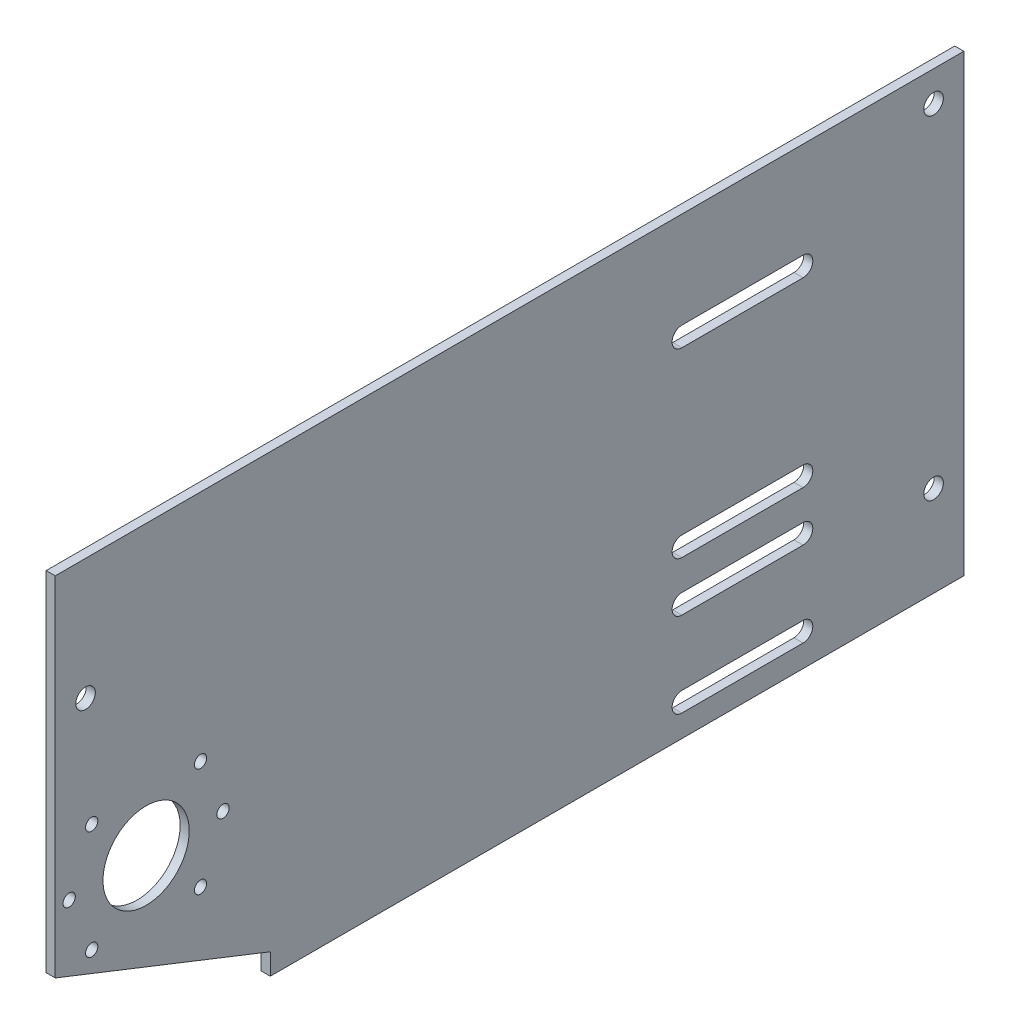
SolidWorks part; units mm, degrees
ref_plane "Front Plane" through (0, 0, 0) normal (0, 0, 1) x (1, 0, 0)
ref_plane "Top Plane" through (0, 0, 0) normal (0, 1, 0) x (1, 0, 0)
ref_plane "Right Plane" through (0, 0, 0) normal (1, 0, 0) x (0, 0, -1)
sketch "Sketch1" plane through (0, 0, 0) normal (1, 0, 0) x (0, 0, -1)
  line L1 (0, 0) -> (300, 0)
  line L2 (0, 0) -> (0, 150)
  line L3 (0, 150) -> (300, 150)
  line L4 (300, 0) -> (300, 150)
  circle A0 centre (30, 55) radius 14.235
  dimension "D1" = 300
  dimension "D5" = 28.47
  dimension "D4" = 55
  dimension "D2" = 150
  dimension "D3" = 30
extrude "Boss-Extrude1" add sketch "Sketch1" along normal blind 3
sketch "Sketch2" plane through (0, 0, 0) normal (-1, 0, 0) x (0, 0, 1)
  line L0 (-246.901, 55) -> (-206.901, 55) construction
  line L1 (-246.901, 58.225) -> (-206.901, 58.225)
  line L2 (-246.901, 51.775) -> (-206.901, 51.775)
  line L3 (-206.901, 115) -> (-246.901, 115) construction
  line L4 (-206.901, 111.77) -> (-246.901, 111.77)
  line L5 (-206.901, 118.23) -> (-246.901, 118.23)
  line L6 (-246.901, 38.55) -> (-206.901, 38.55) construction
  line L9 (-246.901, 41.775) -> (-206.901, 41.775)
  line L10 (-246.901, 35.325) -> (-206.901, 35.325)
  line L11 (-246.901, 10.55) -> (-206.901, 10.55) construction
  line L12 (-246.901, 13.775) -> (-206.901, 13.775)
  line L13 (-246.901, 7.325) -> (-206.901, 7.325)
  line L14 (0, 0) -> (-300, 0) construction
  line L15 (-300, 150) -> (0, 150) construction
  line L16 (-300, 0) -> (-300, 150) construction
  line L17 (0, 150) -> (0, 0) construction
  arc A0 (-246.901, 58.225) -> (-246.901, 51.775) centre (-246.901, 55) ccw
  arc A1 (-206.901, 51.775) -> (-206.901, 58.225) centre (-206.901, 55) ccw
  arc A3 (-206.901, 111.77) -> (-206.901, 118.23) centre (-206.901, 115) ccw
  arc A4 (-246.901, 118.23) -> (-246.901, 111.77) centre (-246.901, 115) ccw
  arc A7 (-246.901, 41.775) -> (-246.901, 35.325) centre (-246.901, 38.55) ccw
  arc A8 (-206.901, 35.325) -> (-206.901, 41.775) centre (-206.901, 38.55) ccw
  arc A9 (-246.901, 13.775) -> (-246.901, 7.325) centre (-246.901, 10.55) ccw
  arc A10 (-206.901, 7.325) -> (-206.901, 13.775) centre (-206.901, 10.55) ccw
  circle A11 centre (-290, 140) radius 3.225
  circle A12 centre (-10, 110) radius 3.225
  circle A13 centre (-290, 30) radius 3.225
  point P2 (-226.901, 55)
  point P7 (-216.901, 10.55)
  point P8 (0, 0)
  point P9 (-226.901, 115)
  point P22 (-226.901, 38.55)
  point P34 (-226.901, 10.55)
  dimension "D1" = 3.225
  dimension "D4" = 3.225
  dimension "D6" = 40
  dimension "D8" = 3.225
  dimension "D13" = 6.45
  dimension "D14" = 6.45
  dimension "D15" = 6.45
  dimension "D3" = 40
  dimension "D5" = 40
  dimension "D7" = 10
  dimension "D9" = 40
  dimension "D10" = 60
  dimension "D11" = 28
  dimension "D12" = 55
  dimension "D16" = 10
  dimension "D17" = 10
  dimension "D18" = 30
  dimension "D19" = 10
  dimension "D20" = 10
  dimension "D21" = 110
extrude "Cut-Extrude1" cut sketch "Sketch2" against normal up to next
sketch "Sketch4" plane through (3, 0, 0) normal (1, 0, 0) x (0, 0, -1)
  line L4 (0, 150) -> (0, 0)
  line L5 (0, 0) -> (300, 0)
  line L6 (300, 0) -> (300, 150)
  line L7 (300, 150) -> (0, 150)
  line L8 (0, 150) -> (0, 0)
  line L9 (0, 0) -> (300, 0)
  line L10 (300, 0) -> (300, 150)
  line L11 (300, 150) -> (0, 150)
  circle A0 centre (47.9605, 37.0395) radius 2.0193 construction
  circle A1 centre (47.9605, 37.0395) radius 2.0193
  circle A2 centre (47.9605, 72.9605) radius 2.0193 construction
  circle A3 centre (47.9605, 72.9605) radius 2.0193
  circle A4 centre (55.4, 55) radius 2.0193 construction
  circle A5 centre (55.4, 55) radius 2.0193
  circle A6 centre (12.0395, 72.9605) radius 2.0193 construction
  circle A7 centre (12.0395, 72.9605) radius 2.0193
  circle A8 centre (4.6, 55) radius 2.0193 construction
  circle A9 centre (4.6, 55) radius 2.0193
  circle A10 centre (12.0395, 37.0395) radius 2.0193 construction
  circle A11 centre (12.0395, 37.0395) radius 2.0193
  dimension "D1" = 0
extrude "Cut-Extrude4" cut sketch "Sketch4" against normal through all contours A11 | A7 | A9 | A1 | A5 | A3 region at (3, 37.0395, -12.0395)
sketch "Sketch5" plane through (0, 0, 0) normal (-1, 0, 0) x (0, 0, 1)
  line L0 (-71, 7) -> (0, 35)
  line L1 (0, 150) -> (0, 0) construction
  line L2 (0, 35) -> (0, 0)
  line L3 (0, 0) -> (-71, 0)
  line L4 (-71, 7) -> (-71, 0) construction
  line L5 (0, 0) -> (-300, 0) construction
  line L6 (-71, 0) -> (-71, 7)
  dimension "D1" = 35
extrude "Cut-Extrude5" cut sketch "Sketch5" against normal through all
